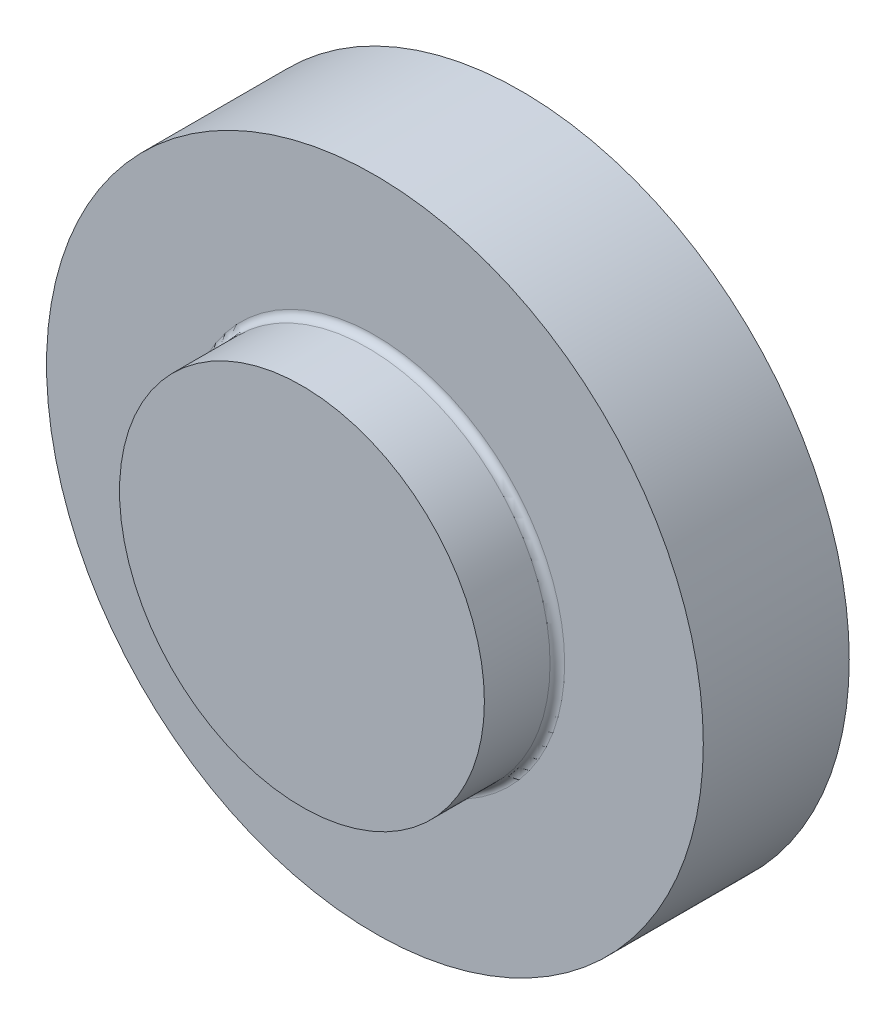
SolidWorks part; units mm, degrees
ref_plane "前视基准面" through (0, 0, 0) normal (0, 0, 1) x (1, 0, 0)
ref_plane "上视基准面" through (0, 0, 0) normal (0, 1, 0) x (1, 0, 0)
ref_plane "右视基准面" through (0, 0, 0) normal (1, 0, 0) x (0, 0, -1)
other "Configuration Table"
sketch "Sketch1" plane through (0, 0, 0) normal (0, 0, 1) x (1, 0, 0)
  circle A0 centre (0, 0) radius 90
extrude "Boss-Extrude1" add sketch "Sketch1" along normal blind 40
ref_plane "Plane1" through (0, 0, 40) normal (0, 0, 1) x (1, 0, 0)
sketch "Sketch2" plane through (0, 0, 40) normal (0, 0, 1) x (1, 0, 0)
  circle A0 centre (0, 0) radius 50
extrude "Boss-Extrude2" add sketch "Sketch2" along normal blind 20
fillet "Fillet1" radius 2 1 edges at (50, 0, 40)
ref_plane "bottom_face" through (0, 0, 0) normal (0, 0, 1) x (1, 0, 0)
ref_plane "top_boss_face" through (0, 0, 60) normal (0, 0, 1) x (1, 0, 0)
sketch3d "3DSketch1"
  line L0 (0, 0, 0) -> (0, 0, 1000) construction
ref_axis "center_axis_z" through (0, 0, 0) along (0, 0, 1)
sketch3d "3DSketch2"
  line L0 (0, 0, 0) -> (0, 0, 1000) construction
ref_axis "shoulder_mount_axis_z" through (0, 0, 0) along (0, 0, 1)
